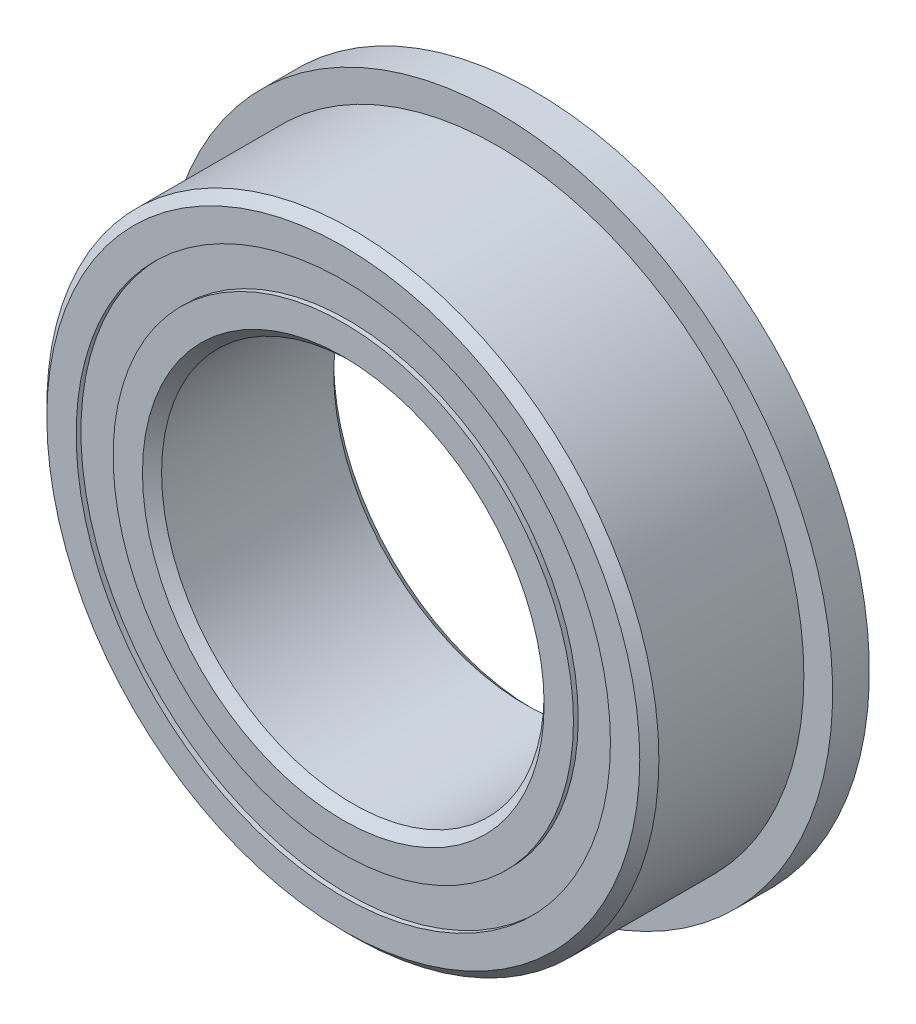
SolidWorks part; units mm, degrees
ref_plane "Front Plane" through (0, 0, 0) normal (0, 0, 1) x (1, 0, 0)
ref_plane "Top Plane" through (0, 0, 0) normal (0, 1, 0) x (1, 0, 0)
ref_plane "Right Plane" through (0, 0, 0) normal (1, 0, 0) x (0, 0, -1)
sketch "Sketch1" plane through (0, 0, 0) normal (1, 0, 0) x (0, 0, -1)
  line L0 (-1.9844, 0) -> (1.9844, 0) construction
  line L1 (0, 6.35) -> (0, -6.35) construction
  line L2 (1.7859, 6.35) -> (-1.7859, 6.35)
  line L3 (-1.7859, 6.35) -> (-1.9844, 6.1516)
  line L4 (-1.9844, 6.1516) -> (-1.9844, 5.5432)
  line L5 (-1.9844, 5.5432) -> (-0.8819, 5.5432)
  line L6 (1.9844, 5.5432) -> (0.8819, 5.5432)
  line L7 (1.9844, 6.1516) -> (1.9844, 5.5432)
  line L8 (1.7859, 6.35) -> (1.9844, 6.1516)
  line L9 (0, 6.35) -> (0, 5.1594) construction
  line L10 (0, 5.1594) -> (0, 3.9688) construction
  arc A0 (-0.8819, 5.5432) -> (0.8819, 5.5432) centre (0, 5.1594) cw
  point P14 (0, 3.9688)
  dimension "Width" = 3.9688
  dimension "OD" = 12.7
  dimension "D1" = 45
  dimension "D2" = 0.1984
  dimension "Shaft Dia" = 7.9375
  dimension "D3" = 1.7639
  dimension "D4" = 0.3838
revolve "Revolve1" add sketch "Sketch1" angle 360 about L0
sketch "Sketch3" plane through (0, 0, 0) normal (1, 0, 0) x (0, 0, -1)
  line L0 (-1.9844, 4.7756) -> (-0.8819, 4.7756)
  line L1 (0, 6.35) -> (0, -6.35) construction
  line L2 (-1.9844, 6.1516) -> (-1.9844, 5.5432) construction
  line L3 (-1.9844, 4.7756) -> (-1.9844, 4.1672)
  line L4 (-1.7859, 6.35) -> (-1.9844, 6.1516) construction
  line L5 (-1.9844, 4.1672) -> (-1.7859, 3.9688)
  line L6 (-1.7859, 3.9688) -> (1.7859, 3.9688)
  line L7 (1.7859, 6.35) -> (1.7859, -6.35) construction
  line L8 (1.7859, 3.9688) -> (1.9844, 4.1672)
  line L9 (1.9844, -6.1516) -> (1.9844, 6.1516) construction
  line L10 (1.9844, 4.1672) -> (1.9844, 4.7756)
  line L11 (1.9844, 4.7756) -> (0.8819, 4.7756)
  line L13 (1.7859, 6.35) -> (1.9844, 6.1516) construction
  arc A0 (0.8819, 5.5432) -> (-0.8819, 5.5432) centre (0, 5.1594) ccw construction
  arc A1 (0.8819, 4.7756) -> (-0.8819, 4.7756) centre (0, 5.1594) cw
revolve "Revolve3" add sketch "Sketch3" angle 360 about L0
sketch "Sketch4" plane through (0, 0, 0) normal (1, 0, 0) x (0, 0, -1)
  line L0 (-0.9618, 5.1594) -> (0.9618, 5.1594)
  arc A2 (-0.9618, 5.1594) -> (0.9618, 5.1594) centre (0, 5.1594) cw
  arc A3 (0.8819, 5.5432) -> (-0.8819, 5.5432) centre (0, 5.1594) ccw construction
revolve "Revolve4" add sketch "Sketch4" angle 360 about L0
ref_axis "Axis1" through (0, 0, -1.9844) along (0, 0, 1)
pattern_circular "CirPattern1" count 16 every 22.5 about axis through (0, 0, -1.9844) along (0, 0, 1) of bodies 104
sketch "Sketch5" plane through (0, 0, 0) normal (1, 0, 0) x (0, 0, -1)
  line L0 (-1.9844, 5.5432) -> (-0.8819, 5.5432) construction
  line L1 (-1.8852, 5.5432) -> (-0.9618, 5.5432)
  line L2 (-1.8852, 5.5432) -> (-1.8852, 4.7756)
  line L3 (-1.8852, 4.7756) -> (-0.9618, 4.7756)
  line L4 (-0.9618, 5.5432) -> (-0.9618, 4.7756)
  line L5 (-1.9844, 4.7756) -> (-0.8819, 4.7756) construction
  line L6 (1.9844, 5.5432) -> (0.8819, 5.5432) construction
  line L7 (1.8852, 5.5432) -> (0.9618, 5.5432)
  line L8 (1.8852, 5.5432) -> (1.8852, 4.7756)
  line L9 (1.8852, 4.7756) -> (0.9618, 4.7756)
  line L10 (0.9618, 5.5432) -> (0.9618, 4.7756)
  line L11 (1.9844, 4.7756) -> (0.8819, 4.7756) construction
  line L12 (-1.7859, 6.35) -> (-1.9844, 6.1516) construction
  point P18 (-1.8852, 6.2508)
revolve "Revolve5" add sketch "Sketch5" angle 360 about L0
sketch "Sketch6" plane through (0, 0, 0) normal (1, 0, 0) x (0, 0, -1)
  line L0 (1.9844, 0) -> (-1.9844, 0) construction
  line L1 (1.9844, 5.5432) -> (1.2224, 5.5432)
  line L2 (1.9844, 5.5432) -> (1.9844, 6.9469)
  line L3 (1.9844, 6.9469) -> (1.2224, 6.9469)
  line L4 (1.2224, 5.5432) -> (1.2224, 6.9469)
  dimension "Th" = 0.762
  dimension "Flange OD" = 13.8938
revolve "Revolve6" add sketch "Sketch6" angle 360 about L0
equation "\"D2@Sketch1\" = \"Width@Sketch1\"*.05"
equation "\"D3@Sketch1\" = \"Width@Sketch1\"/2.25"
equation "\"D4@Sketch1\" = (((\"OD@Sketch1\"-\"Width@Sketch1\")/2)/3.25)/3.5"
equation "\"D2@CirPattern1\" = 360/\"Balls@CirPattern1\""
